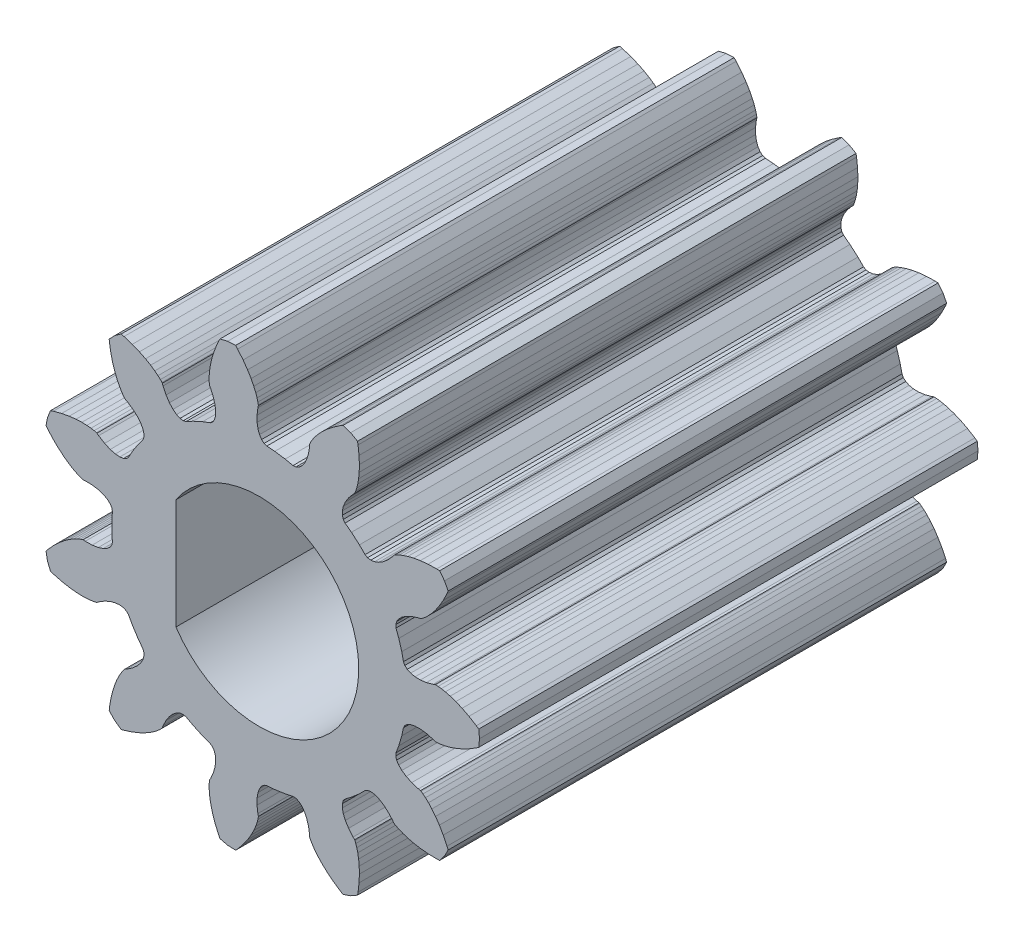
SolidWorks part; units mm, degrees
ref_plane "Front Plane" through (0, 0, 0) normal (0, 0, 1) x (1, 0, 0)
ref_plane "Top Plane" through (0, 0, 0) normal (0, 1, 0) x (1, 0, 0)
ref_plane "Right Plane" through (0, 0, 0) normal (1, 0, 0) x (0, 0, -1)
sketch "Model" plane through (0, 0, 0) normal (0, 0, 1) x (1, 0, 0)
  line L0 (5.4327, -3.7745) -> (5.5806, -3.5864)
  line L1 (5.5806, -3.5864) -> (5.6902, -3.3738)
  line L2 (5.6902, -3.3738) -> (5.6567, -3.291)
  line L3 (5.6567, -3.291) -> (5.5426, -3.0582)
  line L4 (5.5426, -3.0582) -> (5.4257, -2.8575)
  line L5 (5.4257, -2.8575) -> (5.3101, -2.688)
  line L6 (5.3101, -2.688) -> (5.1995, -2.5485)
  line L7 (5.1995, -2.5485) -> (5.0976, -2.4371)
  line L8 (5.0976, -2.4371) -> (5.0076, -2.352)
  line L9 (5.0076, -2.352) -> (4.9328, -2.2906)
  line L10 (4.9328, -2.2906) -> (4.8758, -2.2504)
  line L11 (4.8758, -2.2504) -> (4.8596, -2.2406)
  line L12 (4.8596, -2.2406) -> (4.7952, -2.2284)
  line L13 (4.7952, -2.2284) -> (4.5954, -2.1651)
  line L14 (4.5954, -2.1651) -> (4.4292, -2.0866)
  line L15 (4.4292, -2.0866) -> (4.2977, -1.9975)
  line L16 (4.2977, -1.9975) -> (4.2013, -1.9023)
  line L17 (4.2013, -1.9023) -> (4.14, -1.8056)
  line L18 (4.14, -1.8056) -> (4.1136, -1.7118)
  line L19 (4.1136, -1.7118) -> (4.121, -1.6254)
  line L20 (4.121, -1.6254) -> (4.2052, -1.3996)
  line L21 (4.2052, -1.3996) -> (4.2944, -1.0961)
  line L22 (4.2944, -1.0961) -> (4.3456, -0.8606)
  line L23 (4.3456, -0.8606) -> (4.386, -0.7839)
  line L24 (4.386, -0.7839) -> (4.459, -0.7193)
  line L25 (4.459, -0.7193) -> (4.5628, -0.671)
  line L26 (4.5628, -0.671) -> (4.6954, -0.6431)
  line L27 (4.6954, -0.6431) -> (4.8542, -0.6392)
  line L28 (4.8542, -0.6392) -> (5.0364, -0.6631)
  line L29 (5.0364, -0.6631) -> (5.2387, -0.7178)
  line L30 (5.2387, -0.7178) -> (5.2995, -0.7424)
  line L31 (5.2995, -0.7424) -> (5.3185, -0.7429)
  line L32 (5.3185, -0.7429) -> (5.3881, -0.7398)
  line L33 (5.3881, -0.7398) -> (5.4843, -0.7287)
  line L34 (5.4843, -0.7287) -> (5.606, -0.7057)
  line L35 (5.606, -0.7057) -> (5.7519, -0.6672)
  line L36 (5.7519, -0.6672) -> (5.9204, -0.6095)
  line L37 (5.9204, -0.6095) -> (6.1093, -0.5295)
  line L38 (6.1093, -0.5295) -> (6.3161, -0.4238)
  line L39 (6.3161, -0.4238) -> (6.538, -0.2897)
  line L40 (6.538, -0.2897) -> (6.6109, -0.2382)
  line L41 (6.6109, -0.2382) -> (6.6336, 0)
  line L42 (6.6336, 0) -> (6.6109, 0.2382)
  line L43 (6.6109, 0.2382) -> (6.538, 0.2897)
  line L44 (6.538, 0.2897) -> (6.3161, 0.4238)
  line L45 (6.3161, 0.4238) -> (6.1093, 0.5295)
  line L46 (6.1093, 0.5295) -> (5.9204, 0.6095)
  line L47 (5.9204, 0.6095) -> (5.7519, 0.6672)
  line L48 (5.7519, 0.6672) -> (5.606, 0.7057)
  line L49 (5.606, 0.7057) -> (5.4843, 0.7287)
  line L50 (5.4843, 0.7287) -> (5.3881, 0.7398)
  line L51 (5.3881, 0.7398) -> (5.3185, 0.7429)
  line L52 (5.3185, 0.7429) -> (5.2995, 0.7424)
  line L53 (5.2995, 0.7424) -> (5.2387, 0.7178)
  line L54 (5.2387, 0.7178) -> (5.0364, 0.6631)
  line L55 (5.0364, 0.6631) -> (4.8542, 0.6392)
  line L56 (4.8542, 0.6392) -> (4.6954, 0.6431)
  line L57 (4.6954, 0.6431) -> (4.5628, 0.671)
  line L58 (4.5628, 0.671) -> (4.459, 0.7193)
  line L59 (4.459, 0.7193) -> (4.386, 0.7839)
  line L60 (4.386, 0.7839) -> (4.3456, 0.8606)
  line L61 (4.3456, 0.8606) -> (4.2944, 1.0961)
  line L62 (4.2944, 1.0961) -> (4.2052, 1.3996)
  line L63 (4.2052, 1.3996) -> (4.121, 1.6254)
  line L64 (4.121, 1.6254) -> (4.1136, 1.7118)
  line L65 (4.1136, 1.7118) -> (4.14, 1.8056)
  line L66 (4.14, 1.8056) -> (4.2013, 1.9023)
  line L67 (4.2013, 1.9023) -> (4.2977, 1.9975)
  line L68 (4.2977, 1.9975) -> (4.4292, 2.0866)
  line L69 (4.4292, 2.0866) -> (4.5954, 2.1651)
  line L70 (4.5954, 2.1651) -> (4.7952, 2.2284)
  line L71 (4.7952, 2.2284) -> (4.8596, 2.2406)
  line L72 (4.8596, 2.2406) -> (4.8758, 2.2504)
  line L73 (4.8758, 2.2504) -> (4.9328, 2.2906)
  line L74 (4.9328, 2.2906) -> (5.0076, 2.352)
  line L75 (5.0076, 2.352) -> (5.0976, 2.4371)
  line L76 (5.0976, 2.4371) -> (5.1995, 2.5485)
  line L77 (5.1995, 2.5485) -> (5.3101, 2.688)
  line L78 (5.3101, 2.688) -> (5.4257, 2.8575)
  line L79 (5.4257, 2.8575) -> (5.5426, 3.0582)
  line L80 (5.5426, 3.0582) -> (5.6567, 3.291)
  line L81 (5.6567, 3.291) -> (5.6902, 3.3738)
  line L82 (5.6902, 3.3738) -> (5.5806, 3.5864)
  line L83 (5.5806, 3.5864) -> (5.4327, 3.7745)
  line L84 (5.4327, 3.7745) -> (5.3435, 3.7784)
  line L85 (5.3435, 3.7784) -> (5.0843, 3.7713)
  line L86 (5.0843, 3.7713) -> (4.8532, 3.7484)
  line L87 (4.8532, 3.7484) -> (4.651, 3.7136)
  line L88 (4.651, 3.7136) -> (4.4781, 3.671)
  line L89 (4.4781, 3.671) -> (4.3345, 3.6245)
  line L90 (4.3345, 3.6245) -> (4.2197, 3.578)
  line L91 (4.2197, 3.578) -> (4.1328, 3.5354)
  line L92 (4.1328, 3.5354) -> (4.0725, 3.5004)
  line L93 (4.0725, 3.5004) -> (4.0569, 3.4897)
  line L94 (4.0569, 3.4897) -> (4.019, 3.4361)
  line L95 (4.019, 3.4361) -> (3.8784, 3.2807)
  line L96 (3.8784, 3.2807) -> (3.738, 3.1622)
  line L97 (3.738, 3.1622) -> (3.6023, 3.0795)
  line L98 (3.6023, 3.0795) -> (3.4757, 3.0313)
  line L99 (3.4757, 3.0313) -> (3.3623, 3.0158)
  line L100 (3.3623, 3.0158) -> (3.266, 3.0307)
  line L101 (3.266, 3.0307) -> (3.1905, 3.0734)
  line L102 (3.1905, 3.0734) -> (3.0201, 3.2438)
  line L103 (3.0201, 3.2438) -> (2.781, 3.451)
  line L104 (2.781, 3.451) -> (2.5881, 3.5954)
  line L105 (2.5881, 3.5954) -> (2.5351, 3.664)
  line L106 (2.5351, 3.664) -> (2.5066, 3.7572)
  line L107 (2.5066, 3.7572) -> (2.5058, 3.8717)
  line L108 (2.5058, 3.8717) -> (2.5355, 4.0039)
  line L109 (2.5355, 4.0039) -> (2.598, 4.15)
  line L110 (2.598, 4.15) -> (2.6954, 4.3058)
  line L111 (2.6954, 4.3058) -> (2.8292, 4.4671)
  line L112 (2.8292, 4.4671) -> (2.8768, 4.5122)
  line L113 (2.8768, 4.5122) -> (2.8851, 4.5292)
  line L114 (2.8851, 4.5292) -> (2.9113, 4.5939)
  line L115 (2.9113, 4.5939) -> (2.9411, 4.6859)
  line L116 (2.9411, 4.6859) -> (2.9707, 4.8062)
  line L117 (2.9707, 4.8062) -> (2.9963, 4.955)
  line L118 (2.9963, 4.955) -> (3.0139, 5.1322)
  line L119 (3.0139, 5.1322) -> (3.0195, 5.3372)
  line L120 (3.0195, 5.3372) -> (3.0093, 5.5693)
  line L121 (3.0093, 5.5693) -> (2.9795, 5.8268)
  line L122 (2.9795, 5.8268) -> (2.9629, 5.9145)
  line L123 (2.9629, 5.9145) -> (2.7557, 6.0342)
  line L124 (2.7557, 6.0342) -> (2.5296, 6.1124)
  line L125 (2.5296, 6.1124) -> (2.4525, 6.0675)
  line L126 (2.4525, 6.0675) -> (2.2383, 5.9214)
  line L127 (2.2383, 5.9214) -> (2.0563, 5.7772)
  line L128 (2.0563, 5.7772) -> (1.905, 5.6386)
  line L129 (1.905, 5.6386) -> (1.7826, 5.5093)
  line L130 (1.7826, 5.5093) -> (1.6869, 5.3925)
  line L131 (1.6869, 5.3925) -> (1.6154, 5.2914)
  line L132 (1.6154, 5.2914) -> (1.5653, 5.2085)
  line L133 (1.5653, 5.2085) -> (1.5336, 5.1465)
  line L134 (1.5336, 5.1465) -> (1.5262, 5.129)
  line L135 (1.5262, 5.129) -> (1.5233, 5.0635)
  line L136 (1.5233, 5.0635) -> (1.489, 4.8567)
  line L137 (1.489, 4.8567) -> (1.435, 4.6811)
  line L138 (1.435, 4.6811) -> (1.3656, 4.5382)
  line L139 (1.3656, 4.5382) -> (1.2851, 4.4292)
  line L140 (1.2851, 4.4292) -> (1.198, 4.3549)
  line L141 (1.198, 4.3549) -> (1.109, 4.3153)
  line L142 (1.109, 4.3153) -> (1.0224, 4.3104)
  line L143 (1.0224, 4.3104) -> (0.7869, 4.3616)
  line L144 (0.7869, 4.3616) -> (0.4738, 4.4067)
  line L145 (0.4738, 4.4067) -> (0.2334, 4.4238)
  line L146 (0.2334, 4.4238) -> (0.1517, 4.453)
  line L147 (0.1517, 4.453) -> (0.0774, 4.516)
  line L148 (0.0774, 4.516) -> (0.0148, 4.6119)
  line L149 (0.0148, 4.6119) -> (-0.0317, 4.7391)
  line L150 (-0.0317, 4.7391) -> (-0.0581, 4.8958)
  line L151 (-0.0581, 4.8958) -> (-0.0604, 5.0795)
  line L152 (-0.0604, 5.0795) -> (-0.0351, 5.2876)
  line L153 (-0.0351, 5.2876) -> (-0.0194, 5.3512)
  line L154 (-0.0194, 5.3512) -> (-0.0215, 5.3701)
  line L155 (-0.0215, 5.3701) -> (-0.0345, 5.4386)
  line L156 (-0.0345, 5.4386) -> (-0.0592, 5.5321)
  line L157 (-0.0592, 5.5321) -> (-0.0993, 5.6494)
  line L158 (-0.0993, 5.6494) -> (-0.1582, 5.7883)
  line L159 (-0.1582, 5.7883) -> (-0.2392, 5.9469)
  line L160 (-0.2392, 5.9469) -> (-0.3454, 6.1225)
  line L161 (-0.3454, 6.1225) -> (-0.4794, 6.3121)
  line L162 (-0.4794, 6.3121) -> (-0.6437, 6.5127)
  line L163 (-0.6437, 6.5127) -> (-0.7051, 6.5775)
  line L164 (-0.7051, 6.5775) -> (-0.9441, 6.5661)
  line L165 (-0.9441, 6.5661) -> (-1.1766, 6.5097)
  line L166 (-1.1766, 6.5097) -> (-1.2172, 6.4302)
  line L167 (-1.2172, 6.4302) -> (-1.3184, 6.1915)
  line L168 (-1.3184, 6.1915) -> (-1.3935, 5.9718)
  line L169 (-1.3935, 5.9718) -> (-1.4459, 5.7734)
  line L170 (-1.4459, 5.7734) -> (-1.479, 5.5985)
  line L171 (-1.479, 5.5985) -> (-1.4963, 5.4485)
  line L172 (-1.4963, 5.4485) -> (-1.5018, 5.3247)
  line L173 (-1.5018, 5.3247) -> (-1.4991, 5.228)
  line L174 (-1.4991, 5.228) -> (-1.4922, 5.1586)
  line L175 (-1.4922, 5.1586) -> (-1.489, 5.1399)
  line L176 (-1.489, 5.1399) -> (-1.456, 5.0833)
  line L177 (-1.456, 5.0833) -> (-1.3731, 4.8908)
  line L178 (-1.3731, 4.8908) -> (-1.3236, 4.7138)
  line L179 (-1.3236, 4.7138) -> (-1.3047, 4.5561)
  line L180 (-1.3047, 4.5561) -> (-1.3135, 4.4209)
  line L181 (-1.3135, 4.4209) -> (-1.3466, 4.3112)
  line L182 (-1.3466, 4.3112) -> (-1.4001, 4.2298)
  line L183 (-1.4001, 4.2298) -> (-1.4703, 4.1789)
  line L184 (-1.4703, 4.1789) -> (-1.6961, 4.0947)
  line L185 (-1.6961, 4.0947) -> (-1.9839, 3.9633)
  line L186 (-1.9839, 3.9633) -> (-2.1953, 3.8478)
  line L187 (-2.1953, 3.8478) -> (-2.2798, 3.8281)
  line L188 (-2.2798, 3.8281) -> (-2.3764, 3.8409)
  line L189 (-2.3764, 3.8409) -> (-2.4809, 3.8878)
  line L190 (-2.4809, 3.8878) -> (-2.5888, 3.9697)
  line L191 (-2.5888, 3.9697) -> (-2.6957, 4.0872)
  line L192 (-2.6957, 4.0872) -> (-2.797, 4.2405)
  line L193 (-2.797, 4.2405) -> (-2.8882, 4.4292)
  line L194 (-2.8882, 4.4292) -> (-2.9094, 4.4913)
  line L195 (-2.9094, 4.4913) -> (-2.9214, 4.5059)
  line L196 (-2.9214, 4.5059) -> (-2.9693, 4.5566)
  line L197 (-2.9693, 4.5566) -> (-3.0407, 4.6219)
  line L198 (-3.0407, 4.6219) -> (-3.1378, 4.6989)
  line L199 (-3.1378, 4.6989) -> (-3.2625, 4.7839)
  line L200 (-3.2625, 4.7839) -> (-3.4164, 4.8735)
  line L201 (-3.4164, 4.8735) -> (-3.6006, 4.9638)
  line L202 (-3.6006, 4.9638) -> (-3.8159, 5.0509)
  line L203 (-3.8159, 5.0509) -> (-4.0626, 5.1308)
  line L204 (-4.0626, 5.1308) -> (-4.1492, 5.1521)
  line L205 (-4.1492, 5.1521) -> (-4.3441, 5.0134)
  line L206 (-4.3441, 5.0134) -> (-4.5092, 4.8402)
  line L207 (-4.5092, 4.8402) -> (-4.5004, 4.7514)
  line L208 (-4.5004, 4.7514) -> (-4.4565, 4.4958)
  line L209 (-4.4565, 4.4958) -> (-4.4009, 4.2704)
  line L210 (-4.4009, 4.2704) -> (-4.3377, 4.0752)
  line L211 (-4.3377, 4.0752) -> (-4.2709, 3.9101)
  line L212 (-4.2709, 3.9101) -> (-4.2045, 3.7746)
  line L213 (-4.2045, 3.7746) -> (-4.1421, 3.6675)
  line L214 (-4.1421, 3.6675) -> (-4.0876, 3.5876)
  line L215 (-4.0876, 3.5876) -> (-4.0443, 3.5329)
  line L216 (-4.0443, 3.5329) -> (-4.0315, 3.5189)
  line L217 (-4.0315, 3.5189) -> (-3.9731, 3.4891)
  line L218 (-3.9731, 3.4891) -> (-3.7993, 3.3721)
  line L219 (-3.7993, 3.3721) -> (-3.6619, 3.25)
  line L220 (-3.6619, 3.25) -> (-3.5608, 3.1274)
  line L221 (-3.5608, 3.1274) -> (-3.4951, 3.0089)
  line L222 (-3.4951, 3.0089) -> (-3.4636, 2.8988)
  line L223 (-3.4636, 2.8988) -> (-3.4647, 2.8014)
  line L224 (-3.4647, 2.8014) -> (-3.4962, 2.7206)
  line L225 (-3.4962, 2.7206) -> (-3.6406, 2.5277)
  line L226 (-3.6406, 2.5277) -> (-3.8116, 2.2615)
  line L227 (-3.8116, 2.2615) -> (-3.9271, 2.0501)
  line L228 (-3.9271, 2.0501) -> (-3.9875, 1.9879)
  line L229 (-3.9875, 1.9879) -> (-4.0757, 1.9464)
  line L230 (-4.0757, 1.9464) -> (-4.1889, 1.9293)
  line L231 (-4.1889, 1.9293) -> (-4.324, 1.9399)
  line L232 (-4.324, 1.9399) -> (-4.4775, 1.9809)
  line L233 (-4.4775, 1.9809) -> (-4.6456, 2.0551)
  line L234 (-4.6456, 2.0551) -> (-4.8243, 2.1646)
  line L235 (-4.8243, 2.1646) -> (-4.8757, 2.2054)
  line L236 (-4.8757, 2.2054) -> (-4.8937, 2.2112)
  line L237 (-4.8937, 2.2112) -> (-4.9614, 2.2279)
  line L238 (-4.9614, 2.2279) -> (-5.0568, 2.2443)
  line L239 (-5.0568, 2.2443) -> (-5.1801, 2.2565)
  line L240 (-5.1801, 2.2565) -> (-5.331, 2.2607)
  line L241 (-5.331, 2.2607) -> (-5.5089, 2.2528)
  line L242 (-5.5089, 2.2528) -> (-5.7126, 2.2292)
  line L243 (-5.7126, 2.2292) -> (-5.9408, 2.1861)
  line L244 (-5.9408, 2.1861) -> (-6.1916, 2.1199)
  line L245 (-6.1916, 2.1199) -> (-6.276, 2.091)
  line L246 (-6.276, 2.091) -> (-6.3649, 1.8689)
  line L247 (-6.3649, 1.8689) -> (-6.4102, 1.634)
  line L248 (-6.4102, 1.634) -> (-6.3548, 1.564)
  line L249 (-6.3548, 1.564) -> (-6.1796, 1.3728)
  line L250 (-6.1796, 1.3728) -> (-6.011, 1.2132)
  line L251 (-6.011, 1.2132) -> (-5.8523, 1.0831)
  line L252 (-5.8523, 1.0831) -> (-5.7069, 0.9804)
  line L253 (-5.7069, 0.9804) -> (-5.5777, 0.9023)
  line L254 (-5.5777, 0.9023) -> (-5.4674, 0.8459)
  line L255 (-5.4674, 0.8459) -> (-5.3783, 0.8081)
  line L256 (-5.3783, 0.8081) -> (-5.3123, 0.7856)
  line L257 (-5.3123, 0.7856) -> (-5.294, 0.7807)
  line L258 (-5.294, 0.7807) -> (-5.2288, 0.7872)
  line L259 (-5.2288, 0.7872) -> (-5.0192, 0.7827)
  line L260 (-5.0192, 0.7827) -> (-4.8377, 0.7542)
  line L261 (-4.8377, 0.7542) -> (-4.6864, 0.7058)
  line L262 (-4.6864, 0.7058) -> (-4.567, 0.6417)
  line L263 (-4.567, 0.6417) -> (-4.481, 0.5661)
  line L264 (-4.481, 0.5661) -> (-4.4292, 0.4835)
  line L265 (-4.4292, 0.4835) -> (-4.412, 0.3985)
  line L266 (-4.412, 0.3985) -> (-4.4292, 0.1582)
  line L267 (-4.4292, 0.1582) -> (-4.4292, -0.1582)
  line L268 (-4.4292, -0.1582) -> (-4.412, -0.3985)
  line L269 (-4.412, -0.3985) -> (-4.4292, -0.4835)
  line L270 (-4.4292, -0.4835) -> (-4.481, -0.5661)
  line L271 (-4.481, -0.5661) -> (-4.567, -0.6417)
  line L272 (-4.567, -0.6417) -> (-4.6864, -0.7058)
  line L273 (-4.6864, -0.7058) -> (-4.8377, -0.7542)
  line L274 (-4.8377, -0.7542) -> (-5.0192, -0.7827)
  line L275 (-5.0192, -0.7827) -> (-5.2288, -0.7872)
  line L276 (-5.2288, -0.7872) -> (-5.294, -0.7807)
  line L277 (-5.294, -0.7807) -> (-5.3123, -0.7856)
  line L278 (-5.3123, -0.7856) -> (-5.3783, -0.8081)
  line L279 (-5.3783, -0.8081) -> (-5.4674, -0.8459)
  line L280 (-5.4674, -0.8459) -> (-5.5777, -0.9023)
  line L281 (-5.5777, -0.9023) -> (-5.7069, -0.9804)
  line L282 (-5.7069, -0.9804) -> (-5.8523, -1.0831)
  line L283 (-5.8523, -1.0831) -> (-6.011, -1.2132)
  line L284 (-6.011, -1.2132) -> (-6.1796, -1.3728)
  line L285 (-6.1796, -1.3728) -> (-6.3548, -1.564)
  line L286 (-6.3548, -1.564) -> (-6.4102, -1.634)
  line L287 (-6.4102, -1.634) -> (-6.3649, -1.8689)
  line L288 (-6.3649, -1.8689) -> (-6.276, -2.091)
  line L289 (-6.276, -2.091) -> (-6.1916, -2.1199)
  line L290 (-6.1916, -2.1199) -> (-5.9408, -2.1861)
  line L291 (-5.9408, -2.1861) -> (-5.7126, -2.2292)
  line L292 (-5.7126, -2.2292) -> (-5.5089, -2.2528)
  line L293 (-5.5089, -2.2528) -> (-5.331, -2.2607)
  line L294 (-5.331, -2.2607) -> (-5.1801, -2.2565)
  line L295 (-5.1801, -2.2565) -> (-5.0568, -2.2443)
  line L296 (-5.0568, -2.2443) -> (-4.9614, -2.2279)
  line L297 (-4.9614, -2.2279) -> (-4.8937, -2.2112)
  line L298 (-4.8937, -2.2112) -> (-4.8757, -2.2054)
  line L299 (-4.8757, -2.2054) -> (-4.8243, -2.1646)
  line L300 (-4.8243, -2.1646) -> (-4.6456, -2.0551)
  line L301 (-4.6456, -2.0551) -> (-4.4775, -1.9809)
  line L302 (-4.4775, -1.9809) -> (-4.324, -1.9399)
  line L303 (-4.324, -1.9399) -> (-4.1889, -1.9293)
  line L304 (-4.1889, -1.9293) -> (-4.0757, -1.9464)
  line L305 (-4.0757, -1.9464) -> (-3.9875, -1.9879)
  line L306 (-3.9875, -1.9879) -> (-3.9271, -2.0501)
  line L307 (-3.9271, -2.0501) -> (-3.8116, -2.2615)
  line L308 (-3.8116, -2.2615) -> (-3.6406, -2.5277)
  line L309 (-3.6406, -2.5277) -> (-3.4962, -2.7206)
  line L310 (-3.4962, -2.7206) -> (-3.4647, -2.8014)
  line L311 (-3.4647, -2.8014) -> (-3.4636, -2.8988)
  line L312 (-3.4636, -2.8988) -> (-3.4951, -3.0089)
  line L313 (-3.4951, -3.0089) -> (-3.5608, -3.1274)
  line L314 (-3.5608, -3.1274) -> (-3.6619, -3.25)
  line L315 (-3.6619, -3.25) -> (-3.7993, -3.3721)
  line L316 (-3.7993, -3.3721) -> (-3.9731, -3.4891)
  line L317 (-3.9731, -3.4891) -> (-4.0315, -3.5189)
  line L318 (-4.0315, -3.5189) -> (-4.0443, -3.5329)
  line L319 (-4.0443, -3.5329) -> (-4.0876, -3.5876)
  line L320 (-4.0876, -3.5876) -> (-4.1421, -3.6675)
  line L321 (-4.1421, -3.6675) -> (-4.2045, -3.7746)
  line L322 (-4.2045, -3.7746) -> (-4.2709, -3.9101)
  line L323 (-4.2709, -3.9101) -> (-4.3377, -4.0752)
  line L324 (-4.3377, -4.0752) -> (-4.4009, -4.2704)
  line L325 (-4.4009, -4.2704) -> (-4.4565, -4.4958)
  line L326 (-4.4565, -4.4958) -> (-4.5004, -4.7514)
  line L327 (-4.5004, -4.7514) -> (-4.5092, -4.8402)
  line L328 (-4.5092, -4.8402) -> (-4.3441, -5.0134)
  line L329 (-4.3441, -5.0134) -> (-4.1492, -5.1521)
  line L330 (-4.1492, -5.1521) -> (-4.0626, -5.1308)
  line L331 (-4.0626, -5.1308) -> (-3.8159, -5.0509)
  line L332 (-3.8159, -5.0509) -> (-3.6006, -4.9638)
  line L333 (-3.6006, -4.9638) -> (-3.4164, -4.8735)
  line L334 (-3.4164, -4.8735) -> (-3.2625, -4.7839)
  line L335 (-3.2625, -4.7839) -> (-3.1378, -4.6989)
  line L336 (-3.1378, -4.6989) -> (-3.0407, -4.6219)
  line L337 (-3.0407, -4.6219) -> (-2.9693, -4.5566)
  line L338 (-2.9693, -4.5566) -> (-2.9214, -4.5059)
  line L339 (-2.9214, -4.5059) -> (-2.9094, -4.4913)
  line L340 (-2.9094, -4.4913) -> (-2.8882, -4.4292)
  line L341 (-2.8882, -4.4292) -> (-2.797, -4.2405)
  line L342 (-2.797, -4.2405) -> (-2.6957, -4.0872)
  line L343 (-2.6957, -4.0872) -> (-2.5888, -3.9697)
  line L344 (-2.5888, -3.9697) -> (-2.4809, -3.8878)
  line L345 (-2.4809, -3.8878) -> (-2.3764, -3.8409)
  line L346 (-2.3764, -3.8409) -> (-2.2798, -3.8281)
  line L347 (-2.2798, -3.8281) -> (-2.1953, -3.8478)
  line L348 (-2.1953, -3.8478) -> (-1.9839, -3.9633)
  line L349 (-1.9839, -3.9633) -> (-1.6961, -4.0947)
  line L350 (-1.6961, -4.0947) -> (-1.4703, -4.1789)
  line L351 (-1.4703, -4.1789) -> (-1.4001, -4.2298)
  line L352 (-1.4001, -4.2298) -> (-1.3466, -4.3112)
  line L353 (-1.3466, -4.3112) -> (-1.3135, -4.4209)
  line L354 (-1.3135, -4.4209) -> (-1.3047, -4.5561)
  line L355 (-1.3047, -4.5561) -> (-1.3236, -4.7138)
  line L356 (-1.3236, -4.7138) -> (-1.3731, -4.8908)
  line L357 (-1.3731, -4.8908) -> (-1.456, -5.0833)
  line L358 (-1.456, -5.0833) -> (-1.489, -5.1399)
  line L359 (-1.489, -5.1399) -> (-1.4922, -5.1586)
  line L360 (-1.4922, -5.1586) -> (-1.4991, -5.228)
  line L361 (-1.4991, -5.228) -> (-1.5018, -5.3247)
  line L362 (-1.5018, -5.3247) -> (-1.4963, -5.4485)
  line L363 (-1.4963, -5.4485) -> (-1.479, -5.5985)
  line L364 (-1.479, -5.5985) -> (-1.4459, -5.7734)
  line L365 (-1.4459, -5.7734) -> (-1.3935, -5.9718)
  line L366 (-1.3935, -5.9718) -> (-1.3184, -6.1915)
  line L367 (-1.3184, -6.1915) -> (-1.2172, -6.4302)
  line L368 (-1.2172, -6.4302) -> (-1.1766, -6.5097)
  line L369 (-1.1766, -6.5097) -> (-0.9441, -6.5661)
  line L370 (-0.9441, -6.5661) -> (-0.7051, -6.5775)
  line L371 (-0.7051, -6.5775) -> (-0.6437, -6.5127)
  line L372 (-0.6437, -6.5127) -> (-0.4794, -6.3121)
  line L373 (-0.4794, -6.3121) -> (-0.3454, -6.1225)
  line L374 (-0.3454, -6.1225) -> (-0.2392, -5.9469)
  line L375 (-0.2392, -5.9469) -> (-0.1582, -5.7883)
  line L376 (-0.1582, -5.7883) -> (-0.0993, -5.6494)
  line L377 (-0.0993, -5.6494) -> (-0.0592, -5.5321)
  line L378 (-0.0592, -5.5321) -> (-0.0345, -5.4386)
  line L379 (-0.0345, -5.4386) -> (-0.0215, -5.3701)
  line L380 (-0.0215, -5.3701) -> (-0.0194, -5.3512)
  line L381 (-0.0194, -5.3512) -> (-0.0351, -5.2876)
  line L382 (-0.0351, -5.2876) -> (-0.0604, -5.0795)
  line L383 (-0.0604, -5.0795) -> (-0.0581, -4.8958)
  line L384 (-0.0581, -4.8958) -> (-0.0317, -4.7391)
  line L385 (-0.0317, -4.7391) -> (0.0148, -4.6119)
  line L386 (0.0148, -4.6119) -> (0.0774, -4.516)
  line L387 (0.0774, -4.516) -> (0.1517, -4.453)
  line L388 (0.1517, -4.453) -> (0.2334, -4.4238)
  line L389 (0.2334, -4.4238) -> (0.4738, -4.4067)
  line L390 (0.4738, -4.4067) -> (0.7869, -4.3616)
  line L391 (0.7869, -4.3616) -> (1.0224, -4.3104)
  line L392 (1.0224, -4.3104) -> (1.109, -4.3153)
  line L393 (1.109, -4.3153) -> (1.198, -4.3549)
  line L394 (1.198, -4.3549) -> (1.2851, -4.4292)
  line L395 (1.2851, -4.4292) -> (1.3656, -4.5382)
  line L396 (1.3656, -4.5382) -> (1.435, -4.6811)
  line L397 (1.435, -4.6811) -> (1.489, -4.8567)
  line L398 (1.489, -4.8567) -> (1.5233, -5.0635)
  line L399 (1.5233, -5.0635) -> (1.5262, -5.129)
  line L400 (1.5262, -5.129) -> (1.5336, -5.1465)
  line L401 (1.5336, -5.1465) -> (1.5653, -5.2085)
  line L402 (1.5653, -5.2085) -> (1.6154, -5.2914)
  line L403 (1.6154, -5.2914) -> (1.6869, -5.3925)
  line L404 (1.6869, -5.3925) -> (1.7826, -5.5093)
  line L405 (1.7826, -5.5093) -> (1.905, -5.6386)
  line L406 (1.905, -5.6386) -> (2.0563, -5.7772)
  line L407 (2.0563, -5.7772) -> (2.2383, -5.9214)
  line L408 (2.2383, -5.9214) -> (2.4525, -6.0675)
  line L409 (2.4525, -6.0675) -> (2.5296, -6.1124)
  line L410 (2.5296, -6.1124) -> (2.7557, -6.0342)
  line L411 (2.7557, -6.0342) -> (2.9629, -5.9145)
  line L412 (2.9629, -5.9145) -> (2.9795, -5.8268)
  line L413 (2.9795, -5.8268) -> (3.0093, -5.5693)
  line L414 (3.0093, -5.5693) -> (3.0195, -5.3372)
  line L415 (3.0195, -5.3372) -> (3.0139, -5.1322)
  line L416 (3.0139, -5.1322) -> (2.9963, -4.955)
  line L417 (2.9963, -4.955) -> (2.9707, -4.8062)
  line L418 (2.9707, -4.8062) -> (2.9411, -4.6859)
  line L419 (2.9411, -4.6859) -> (2.9113, -4.5939)
  line L420 (2.9113, -4.5939) -> (2.8851, -4.5292)
  line L421 (2.8851, -4.5292) -> (2.8768, -4.5122)
  line L422 (2.8768, -4.5122) -> (2.8292, -4.4671)
  line L423 (2.8292, -4.4671) -> (2.6954, -4.3058)
  line L424 (2.6954, -4.3058) -> (2.598, -4.15)
  line L425 (2.598, -4.15) -> (2.5355, -4.0039)
  line L426 (2.5355, -4.0039) -> (2.5058, -3.8717)
  line L427 (2.5058, -3.8717) -> (2.5066, -3.7572)
  line L428 (2.5066, -3.7572) -> (2.5351, -3.664)
  line L429 (2.5351, -3.664) -> (2.5881, -3.5954)
  line L430 (2.5881, -3.5954) -> (2.781, -3.451)
  line L431 (2.781, -3.451) -> (3.0201, -3.2438)
  line L432 (3.0201, -3.2438) -> (3.1905, -3.0734)
  line L433 (3.1905, -3.0734) -> (3.266, -3.0307)
  line L434 (3.266, -3.0307) -> (3.3623, -3.0158)
  line L435 (3.3623, -3.0158) -> (3.4757, -3.0313)
  line L436 (3.4757, -3.0313) -> (3.6023, -3.0795)
  line L437 (3.6023, -3.0795) -> (3.738, -3.1622)
  line L438 (3.738, -3.1622) -> (3.8784, -3.2807)
  line L439 (3.8784, -3.2807) -> (4.019, -3.4361)
  line L440 (4.019, -3.4361) -> (4.0569, -3.4897)
  line L441 (4.0569, -3.4897) -> (4.0725, -3.5004)
  line L442 (4.0725, -3.5004) -> (4.1328, -3.5354)
  line L443 (4.1328, -3.5354) -> (4.2197, -3.578)
  line L444 (4.2197, -3.578) -> (4.3345, -3.6245)
  line L445 (4.3345, -3.6245) -> (4.4781, -3.671)
  line L446 (4.4781, -3.671) -> (4.651, -3.7136)
  line L447 (4.651, -3.7136) -> (4.8532, -3.7484)
  line L448 (4.8532, -3.7484) -> (5.0843, -3.7713)
  line L449 (5.0843, -3.7713) -> (5.3435, -3.7784)
  line L450 (5.3435, -3.7784) -> (5.4327, -3.7745)
  line L451 (-2.5, 1.6583) -> (-2.5, -1.6583)
  circle A0 centre (0, 0) radius 3
  dimension "D1" = 6
  dimension "D2" = 2.5
extrude "Boss-Extrude1" add sketch "Model" along normal blind 15 contours L449 L450 L0 L1 L2 L3 L4 L5 L6 L7 L8 L9 L10 L11 L12 L13 L14 L15 L16 L17 L18 L19 L20 L21 L22 L23 L24 L25 L26 L27 L28 L29 L30 L31 L32 L33 L34 L35 L36 L37 L38 L39 L40 L41 L42 L43 L44 L45 L46 L47 L48 | L451 A0 region at (5.38, -3.5914, 0) region at (-2.7015, 0, 0)
